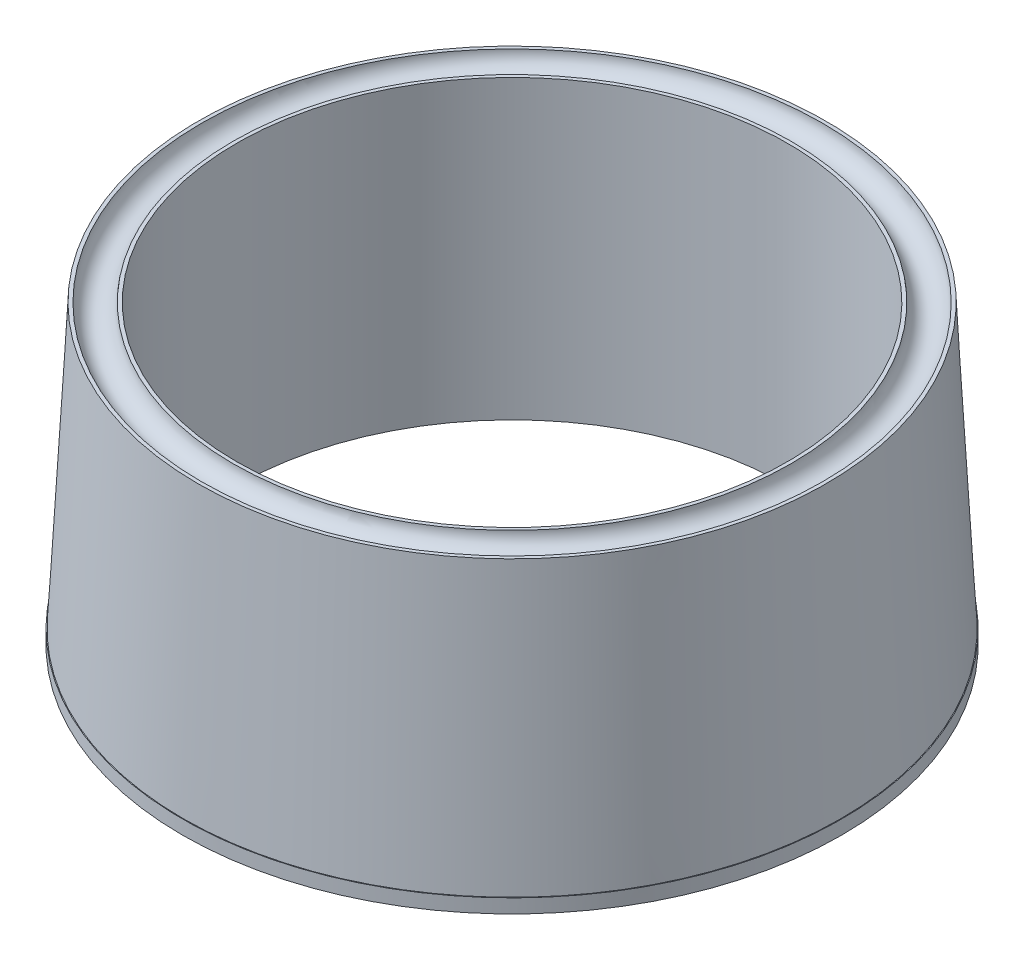
SolidWorks part; units mm, degrees
ref_plane "Płaszczyzna przednia" through (0, 0, 0) normal (0, 0, 1) x (1, 0, 0)
ref_plane "Płaszczyzna górna" through (0, 0, 0) normal (0, 1, 0) x (1, 0, 0)
ref_plane "Płaszczyzna prawa" through (0, 0, 0) normal (1, 0, 0) x (0, 0, -1)
sketch "Sketch1" plane through (0, 0, 0) normal (0, 1, 0) x (1, 0, 0)
  circle A0 centre (0, 0) radius 45
extrude "Boss-Extrude1" add sketch "Sketch1" along normal blind 42.5
sketch "Sketch2" plane through (0, 42.5, 0) normal (0, 1, 0) x (1, 0, 0)
  circle A0 centre (0, 0) radius 39.5
extrude "Cut-Extrude1" cut sketch "Sketch2" against normal blind 148
draft "Draft2" type of draft neutral plane draft angle 3 faces to draft 1 face at (0, 42.5, 45) neutral plane through (0, 42.5, 0) neutral plane normal (0, 1, 0) parameters "D1"=3
sketch "Sketch5" plane through (0, 0, 0) normal (0, -1, 0) x (1, 0, 0)
  line L0 (-39.5, 0) -> (-47.2273, 0)
  circle A0 centre (0, 0) radius 39.5 construction
  circle A1 centre (0, 0) radius 47.2273 construction
  dimension "D1" = 7.7273
sketch "Sketch6" plane through (0, 0, 0) normal (0, -1, 0) x (1, 0, 0)
  line L0 (-39.5, 0) -> (-47.2273, 0) construction
  line L1 (-43.3637, 0) -> (-21.6818, -37.554)
  line L2 (-21.6818, -37.554) -> (21.6818, -37.554)
  line L3 (21.6818, -37.554) -> (43.3637, 0)
  line L4 (43.3637, 0) -> (21.6818, 37.554)
  line L5 (21.6818, 37.554) -> (-21.6818, 37.554)
  line L6 (-21.6818, 37.554) -> (-43.3637, 0)
  line L7 (-21.6818, 34.4295) -> (-18.9759, 35.9918)
  line L8 (-18.9759, 35.9918) -> (-18.9759, 39.1163)
  line L9 (-18.9759, 39.1163) -> (-21.6818, 40.6786)
  line L10 (-21.6818, 40.6786) -> (-24.3878, 39.1163)
  line L11 (-24.3878, 39.1163) -> (-24.3878, 35.9918)
  line L12 (-24.3878, 35.9918) -> (-21.6818, 34.4295)
  line L13 (21.6818, 34.4749) -> (24.3485, 36.0145)
  line L14 (24.3485, 36.0145) -> (24.3485, 39.0936)
  line L15 (24.3485, 39.0936) -> (21.6818, 40.6332)
  line L16 (21.6818, 40.6332) -> (19.0152, 39.0936)
  line L17 (19.0152, 39.0936) -> (19.0152, 36.0145)
  line L18 (19.0152, 36.0145) -> (21.6818, 34.4749)
  line L19 (43.3637, -2.789) -> (45.779, -1.3945)
  line L20 (45.779, -1.3945) -> (45.779, 1.3945)
  line L21 (45.779, 1.3945) -> (43.3637, 2.789)
  line L22 (43.3637, 2.789) -> (40.9483, 1.3945)
  line L23 (40.9483, 1.3945) -> (40.9483, -1.3945)
  line L24 (40.9483, -1.3945) -> (43.3637, -2.789)
  line L25 (-43.3637, -3.3239) -> (-40.4851, -1.662)
  line L26 (-40.4851, -1.662) -> (-40.4851, 1.662)
  line L27 (-40.4851, 1.662) -> (-43.3637, 3.3239)
  line L28 (-43.3637, 3.3239) -> (-46.2423, 1.662)
  line L29 (-46.2423, 1.662) -> (-46.2423, -1.662)
  line L30 (-46.2423, -1.662) -> (-43.3637, -3.3239)
  line L31 (-21.6818, -34.4749) -> (-24.3485, -36.0145)
  line L32 (-24.3485, -36.0145) -> (-24.3485, -39.0936)
  line L33 (-24.3485, -39.0936) -> (-21.6818, -40.6332)
  line L34 (-21.6818, -40.6332) -> (-19.0152, -39.0936)
  line L35 (-19.0152, -39.0936) -> (-19.0152, -36.0145)
  line L36 (-19.0152, -36.0145) -> (-21.6818, -34.4749)
  line L37 (21.6818, -40.2976) -> (24.0579, -38.9258)
  line L38 (24.0579, -38.9258) -> (24.0579, -36.1822)
  line L39 (24.0579, -36.1822) -> (21.6818, -34.8104)
  line L40 (21.6818, -34.8104) -> (19.3058, -36.1822)
  line L41 (19.3058, -36.1822) -> (19.3058, -38.9258)
  line L42 (19.3058, -38.9258) -> (21.6818, -40.2976)
  circle A0 centre (0, 0) radius 37.554 construction
  circle A1 centre (-21.6818, 37.554) radius 2.7059 construction
  circle A2 centre (21.6818, 37.554) radius 2.6666 construction
  circle A3 centre (43.3637, 0) radius 2.4153 construction
  circle A4 centre (-43.3637, 0) radius 2.8786 construction
  circle A5 centre (-21.6818, -37.554) radius 2.6666 construction
  circle A6 centre (21.6818, -37.554) radius 2.376 construction
  dimension "D1" = 0.9851
  dimension "D2" = 0.9851
extrude "Cut-Extrude2" cut sketch "Sketch6" against normal blind 5 contours L11 L12 L6 L5 L8 L9 L10 | L16 L17 L5 L4 L13 L14 L15 | L3 L24 L19 L20 L21 L22 L4 | L41 L42 L37 L38 L39 L3 L2 | L34 L35 L2 L1 L31 L32 L33 | L29 L30 L25 L1 L6 L27 L28 | L26 L27 L6 L1 L25 | L6 L12 L7 L8 L5 | L17 L18 L13 L4 L5 | L23 L24 L3 L4 L22 | L40 L41 L2 L3 L39 | L35 L36 L31 L1 L2 region at (-41.6845, 0, 0) region at (-44.2033, 0, 0) region at (-20.9041, 0, -36.2069) region at (-22.0707, 0, -38.2276) region at (-22.0764, 0, 38.2375) region at (-20.8926, 0, 36.1871) region at (20.9888, 0, -36.3537) region at (22.0283, 0, -38.1542) region at (22.0707, 0, 38.2276) region at (20.9041, 0, 36.2069) region at (41.9547, 0, 0) region at (44.0681, 0, 0)
sketch "Sketch7" plane through (0, 0, 0) normal (0, -1, 0) x (1, 0, 0)
  circle A0 centre (0, 0) radius 47.2273
extrude "Boss-Extrude2" add sketch "Sketch7" against normal blind 2
sketch "Sketch8" plane through (0, 2, 0) normal (0, 1, 0) x (1, 0, 0)
  circle A0 centre (0, 0) radius 39.5
extrude "Cut-Extrude3" cut sketch "Sketch8" against normal blind 66
sketch "Sketch9" plane through (0, 0, 0) normal (0, -1, 0) x (1, 0, 0)
  line L1 (-43.2851, 0) -> (-21.6425, -37.486)
  line L2 (-21.6425, -37.486) -> (21.6425, -37.486)
  line L3 (21.6425, -37.486) -> (43.2851, 0)
  line L4 (43.2851, 0) -> (21.6425, 37.486)
  line L5 (21.6425, 37.486) -> (-21.6425, 37.486)
  line L6 (-21.6425, 37.486) -> (-43.2851, 0)
  circle A0 centre (0, 0) radius 37.486 construction
  circle A1 centre (-43.2851, 0) radius 1.6
  circle A2 centre (-21.6425, 37.486) radius 1.6
  circle A3 centre (21.6425, 37.486) radius 1.6
  circle A4 centre (43.2851, 0) radius 1.6
  circle A5 centre (21.6425, -37.486) radius 1.6
  circle A6 centre (-21.6425, -37.486) radius 1.6
extrude "Cut-Extrude4" cut sketch "Sketch9" against normal blind 15 contours L6 A1 L1 | L1 A1 L6 | L5 A2 L6 | L5 A3 L4 | L4 A3 L5 | L4 A4 L3 | L3 A4 L4 | L2 A5 L3 | L3 A5 L2 | L1 A6 L2 | L2 A6 L1 | A2 region at (-42.4029, 0, 0) region at (-43.7261, 0, 0) region at (-21.2015, 0, -36.722) region at (-21.8631, 0, -37.8679) region at (-21.8631, 0, 37.8679) region at (21.2015, 0, -36.722) region at (21.8631, 0, -37.8679) region at (21.8631, 0, 37.8679) region at (21.2015, 0, 36.722) region at (42.4029, 0, 0) region at (43.7261, 0, 0)
sketch "Sketch10" plane through (0, 42.5, 0) normal (0, 1, 0) x (1, 0, 0)
  circle A2 centre (0, 0) radius 42.25
sweep "Cut-Sweep1" cut path "Sketch10" circular profile diameter 4.5 parameters "D3"=4.5
sketch "Sketch17" plane through (0, 42.5, 0) normal (0, 1, 0) x (1, 0, 0)
